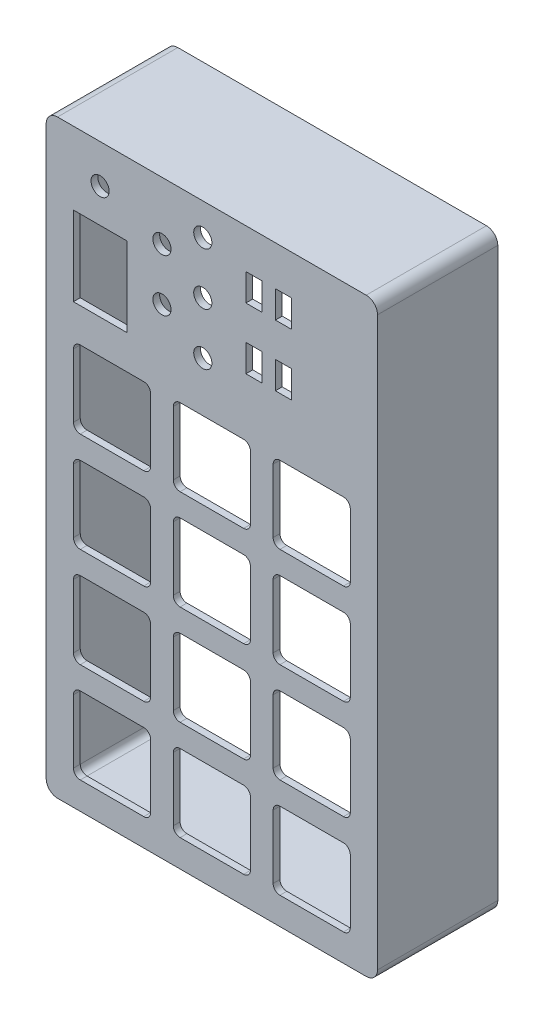
SolidWorks part; units mm, degrees
ref_plane "Alzado" through (0, 0, 0) normal (1, 0, 0) x (0, 1, 0)
ref_plane "Planta" through (0, 0, 0) normal (0, 0, 1) x (0, 1, 0)
ref_plane "Vista lateral" through (0, 0, 0) normal (0, 1, 0) x (-1, 0, 0)
sketch "Croquis1" plane through (0, 0, 0) normal (0, 0, 1) x (0, 1, 0)
  line L0 (70, 0) -> (0, 0) construction
  line L1 (-183, -71) -> (67, -71)
  line L2 (-186, -68) -> (-186, 68)
  line L3 (-183, 71) -> (67, 71)
  line L4 (70, -68) -> (70, 68)
  line L5 (0, 0) -> (0, 71) construction
  line L6 (-176, 61) -> (-176, -61) construction
  line L7 (-173, 61) -> (-145, 61)
  line L8 (-176, 58) -> (-176, 30)
  line L9 (-173, 27) -> (-145, 27)
  line L10 (-142, 58) -> (-142, 30)
  line L11 (-176, -61) -> (-10, -61) construction
  line L12 (-10, -61) -> (-10, 61) construction
  line L13 (-10, 61) -> (-176, 61) construction
  line L14 (-132, 58) -> (-132, 30)
  line L15 (-129, 61) -> (-101, 61)
  line L16 (-98, 58) -> (-98, 30)
  line L17 (-129, 27) -> (-101, 27)
  line L18 (-88, 58) -> (-88, 30)
  line L19 (-85, 61) -> (-57, 61)
  line L20 (-54, 58) -> (-54, 30)
  line L21 (-85, 27) -> (-57, 27)
  line L22 (-44, 58) -> (-44, 30)
  line L23 (-41, 61) -> (-13, 61)
  line L24 (-10, 58) -> (-10, 30)
  line L25 (-41, 27) -> (-13, 27)
  line L26 (-132, 14) -> (-132, -14)
  line L27 (-129, 17) -> (-101, 17)
  line L28 (-98, 14) -> (-98, -14)
  line L29 (-129, -17) -> (-101, -17)
  line L30 (-88, 14) -> (-88, -14)
  line L31 (-85, 17) -> (-57, 17)
  line L32 (-54, 14) -> (-54, -14)
  line L33 (-85, -17) -> (-57, -17)
  line L34 (-44, 14) -> (-44, -14)
  line L35 (-41, 17) -> (-13, 17)
  line L36 (-10, 14) -> (-10, -14)
  line L37 (-41, -17) -> (-13, -17)
  line L38 (-132, -30) -> (-132, -58)
  line L39 (-129, -27) -> (-101, -27)
  line L40 (-98, -30) -> (-98, -58)
  line L41 (-129, -61) -> (-101, -61)
  line L42 (-88, -30) -> (-88, -58)
  line L43 (-85, -27) -> (-57, -27)
  line L44 (-54, -30) -> (-54, -58)
  line L45 (-85, -61) -> (-57, -61)
  line L46 (-44, -30) -> (-44, -58)
  line L47 (-41, -27) -> (-13, -27)
  line L48 (-10, -30) -> (-10, -58)
  line L49 (-41, -61) -> (-13, -61)
  line L50 (-176, 14) -> (-176, -14)
  line L51 (-173, 17) -> (-145, 17)
  line L52 (-142, 14) -> (-142, -14)
  line L53 (-173, -17) -> (-145, -17)
  line L54 (-176, -30) -> (-176, -58)
  line L55 (-173, -27) -> (-145, -27)
  line L56 (-142, -30) -> (-142, -58)
  line L57 (-173, -61) -> (-145, -61)
  line L58 (35, 0) -> (35, -3.8543) construction
  line L59 (5, 61) -> (40, 61)
  line L60 (5, 61) -> (5, 37.5)
  line L61 (5, 37.5) -> (40, 37.5)
  line L62 (40, 61) -> (40, 37.5)
  line L63 (12, 4) -> (35, 4) construction
  line L64 (-188, -68) -> (-188, 68)
  line L65 (15.5, -15) -> (27.5, -15)
  line L66 (15.5, -15) -> (15.5, -22)
  line L67 (15.5, -22) -> (27.5, -22)
  line L68 (27.5, -15) -> (27.5, -22)
  line L69 (42.5, -15) -> (54.5, -15)
  line L70 (42.5, -15) -> (42.5, -22)
  line L71 (42.5, -22) -> (54.5, -22)
  line L72 (54.5, -15) -> (54.5, -22)
  line L73 (15.5, -28) -> (27.5, -28)
  line L74 (15.5, -28) -> (15.5, -35)
  line L75 (15.5, -35) -> (27.5, -35)
  line L76 (27.5, -28) -> (27.5, -35)
  line L77 (42.5, -28) -> (54.5, -28)
  line L78 (42.5, -28) -> (42.5, -35)
  line L79 (42.5, -35) -> (54.5, -35)
  line L80 (54.5, -28) -> (54.5, -35)
  line L81 (-183, 73) -> (67, 73)
  line L82 (72, -68) -> (72, 68)
  line L83 (-183, -73) -> (67, -73)
  line L84 (0, 0) -> (0, -71) construction
  arc A0 (-145, 61) -> (-142, 58) centre (-145, 58) cw
  arc A1 (-145, 27) -> (-142, 30) centre (-145, 30) ccw
  arc A2 (-176, 30) -> (-173, 27) centre (-173, 30) ccw
  arc A3 (-173, 61) -> (-176, 58) centre (-173, 58) ccw
  arc A4 (-129, 61) -> (-132, 58) centre (-129, 58) ccw
  arc A5 (-132, 30) -> (-129, 27) centre (-129, 30) ccw
  arc A6 (-101, 61) -> (-98, 58) centre (-101, 58) cw
  arc A7 (-101, 27) -> (-98, 30) centre (-101, 30) ccw
  arc A8 (-85, 61) -> (-88, 58) centre (-85, 58) ccw
  arc A9 (-88, 30) -> (-85, 27) centre (-85, 30) ccw
  arc A10 (-57, 61) -> (-54, 58) centre (-57, 58) cw
  arc A11 (-57, 27) -> (-54, 30) centre (-57, 30) ccw
  arc A12 (-41, 61) -> (-44, 58) centre (-41, 58) ccw
  arc A13 (-44, 30) -> (-41, 27) centre (-41, 30) ccw
  arc A14 (-13, 61) -> (-10, 58) centre (-13, 58) cw
  arc A15 (-13, 27) -> (-10, 30) centre (-13, 30) ccw
  arc A16 (-129, 17) -> (-132, 14) centre (-129, 14) ccw
  arc A17 (-132, -14) -> (-129, -17) centre (-129, -14) ccw
  arc A18 (-101, 17) -> (-98, 14) centre (-101, 14) cw
  arc A19 (-101, -17) -> (-98, -14) centre (-101, -14) ccw
  arc A20 (-85, 17) -> (-88, 14) centre (-85, 14) ccw
  arc A21 (-88, -14) -> (-85, -17) centre (-85, -14) ccw
  arc A22 (-57, 17) -> (-54, 14) centre (-57, 14) cw
  arc A23 (-57, -17) -> (-54, -14) centre (-57, -14) ccw
  arc A24 (-41, 17) -> (-44, 14) centre (-41, 14) ccw
  arc A25 (-44, -14) -> (-41, -17) centre (-41, -14) ccw
  arc A26 (-13, 17) -> (-10, 14) centre (-13, 14) cw
  arc A27 (-13, -17) -> (-10, -14) centre (-13, -14) ccw
  arc A28 (-129, -27) -> (-132, -30) centre (-129, -30) ccw
  arc A29 (-132, -58) -> (-129, -61) centre (-129, -58) ccw
  arc A30 (-101, -27) -> (-98, -30) centre (-101, -30) cw
  arc A31 (-101, -61) -> (-98, -58) centre (-101, -58) ccw
  arc A32 (-85, -27) -> (-88, -30) centre (-85, -30) ccw
  arc A33 (-88, -58) -> (-85, -61) centre (-85, -58) ccw
  arc A34 (-57, -27) -> (-54, -30) centre (-57, -30) cw
  arc A35 (-57, -61) -> (-54, -58) centre (-57, -58) ccw
  arc A36 (-41, -27) -> (-44, -30) centre (-41, -30) ccw
  arc A37 (-44, -58) -> (-41, -61) centre (-41, -58) ccw
  arc A38 (-13, -27) -> (-10, -30) centre (-13, -30) cw
  arc A39 (-13, -61) -> (-10, -58) centre (-13, -58) ccw
  arc A40 (-173, 17) -> (-176, 14) centre (-173, 14) ccw
  arc A41 (-176, -14) -> (-173, -17) centre (-173, -14) ccw
  arc A42 (-145, 17) -> (-142, 14) centre (-145, 14) cw
  arc A43 (-145, -17) -> (-142, -14) centre (-145, -14) ccw
  arc A44 (-173, -27) -> (-176, -30) centre (-173, -30) ccw
  arc A45 (-176, -58) -> (-173, -61) centre (-173, -58) ccw
  arc A46 (-145, -27) -> (-142, -30) centre (-145, -30) cw
  arc A47 (-145, -61) -> (-142, -58) centre (-145, -58) ccw
  circle A48 centre (55, 49.25) radius 4
  circle A49 centre (23.5, 22) radius 4
  circle A50 centre (46.5, 22) radius 4
  circle A51 centre (12, 4) radius 4
  circle A52 centre (35, 4) radius 4
  circle A53 centre (58, 4) radius 4
  circle A54 centre (23.5, 22) radius 6 construction
  circle A55 centre (35, 4) radius 6 construction
  arc A56 (67, 71) -> (70, 68) centre (67, 68) cw
  arc A57 (67, -71) -> (70, -68) centre (67, -68) ccw
  arc A58 (-183, -71) -> (-186, -68) centre (-183, -68) cw
  arc A59 (-186, 68) -> (-183, 71) centre (-183, 68) cw
  arc A60 (-188, 68) -> (-183, 73) centre (-183, 68) cw
  arc A61 (67, 73) -> (72, 68) centre (67, 68) cw
  arc A62 (67, -73) -> (72, -68) centre (67, -68) ccw
  arc A63 (-183, -73) -> (-188, -68) centre (-183, -68) cw
  point P0 (0, 0)
  point P17 (-142, 27)
  point P20 (-176, 27)
  point P26 (-10, 0)
  point P29 (40, 49.25)
  point P175 (23.5, 4)
  point P180 (35, 0)
  dimension "D2" = 3
  dimension "D13" = 8
  dimension "D16" = 8
  dimension "D20" = 12
  dimension "D21" = 12
  dimension "D26" = 3
  dimension "D1" = 34
  dimension "D5" = 10
  dimension "D6" = 10
  dimension "D7" = 10
  dimension "D8" = 10
  dimension "D9" = 10
  dimension "D10" = 35
  dimension "D11" = 23.5
  dimension "D12" = 5
  dimension "D14" = 15
  dimension "D15" = 15
  dimension "D17" = 12
  dimension "D18" = 4
  dimension "D19" = 18
  dimension "D22" = 7
  dimension "D23" = 15
  dimension "D24" = 15
  dimension "D25" = 6
  dimension "D28" = 142
  dimension "D29" = 70
  dimension "D27" = 2
  dimension "D3" = 4
  dimension "D4" = 3
extrude "Saliente-Extruir1" add sketch "Croquis1" along normal blind 3 contours A59 L2 A58 L1 A57 L4 A56 L3 A53 A52 A51 A50 A49 A48 A47 L57 A45 L54 A44 L55 A46 L56 A43 L53 A41 L50 A40 L51 A42 L52 A39 L49 A37 L46 A36 L47 A38 L48 A35 L45 A33 | A63 L83 A62 L82 A61 L81 A60 L64 L2 A59 L3 A56 L4 A57 L1 A58 region at (68.0513, -183.0513, 0) region at (0, -187.7018, 0)
extrude "Saliente-Extruir2" add sketch "Croquis1<3>" against normal blind 50 contours A63 L83 A62 L82 A61 L81 A60 L64 L2 A59 L3 A56 L4 A57 L1 A58 region at (0, -187.7018, 0)
sketch "Croquis1<3>" plane through (0, 0, 0) normal (0, 0, 1) x (0, 1, 0) same geometry as "Croquis1"
